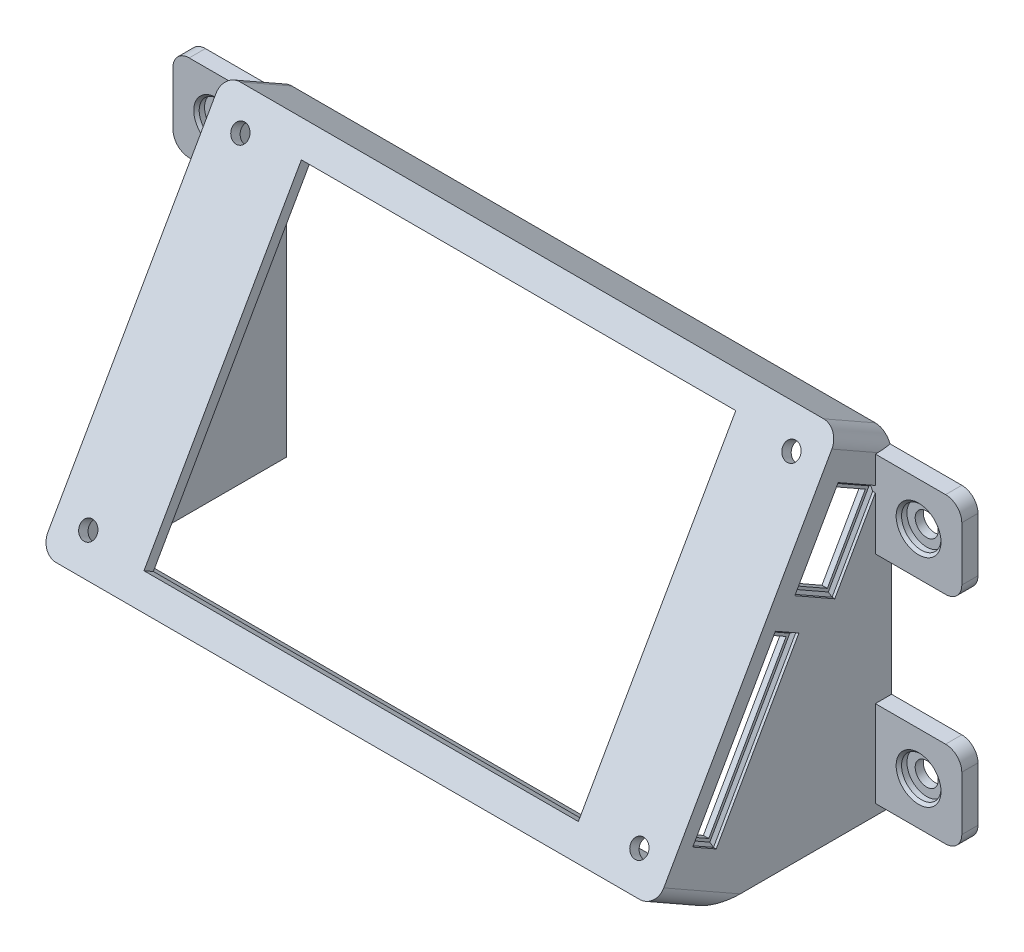
SolidWorks part; units mm, degrees
ref_plane "Front Plane" through (0, 0, 0) normal (0, 0, 1) x (1, 0, 0)
ref_plane "Top Plane" through (0, 0, 0) normal (0, 1, 0) x (1, 0, 0)
ref_plane "Right Plane" through (0, 0, 0) normal (1, 0, 0) x (0, 0, -1)
sketch "Sketch1" plane through (0, 0, 0) normal (1, 0, 0) x (0, 0, -1)
  line L0 (0, 0) -> (0, 60)
  line L1 (0, 60) -> (-34.0735, 0)
  line L2 (-34.0735, 0) -> (0, 0)
  dimension "D1" = 60
  dimension "D2" = 69
extrude "Boss-Extrude1" add sketch "Sketch1" along normal blind 114
sketch "Sketch2" plane through (0, 14.6314, 25.7644) normal (0, 0.4938, 0.8696) x (1, 0, 0)
  line L1 (0, 52.1739) -> (114, 52.1739)
  line L2 (0, 52.1739) -> (0, -16.8261)
  line L3 (0, -16.8261) -> (114, -16.8261)
  line L4 (114, 52.1739) -> (114, -16.8261)
extrude "Boss-Extrude2" add sketch "Sketch2" along normal blind 11
fillet "Fillet1" radius 3 4 edges at (0, 2.716, 38.8561) (0, 62.716, 4.7826) (114, 2.716, 38.8561) (114, 62.716, 4.7826)
shell "Shell1" thickness 2 removed face at (57, 0, 21.11) removed face at (57, 39.0882, 0)
sketch "Sketch3" plane through (0, 20.0634, 35.3296) normal (0, 0.4938, 0.8696) x (1, 0, 0)
  line L0 (0, 49.1739) -> (0, -13.8261) construction
  line L1 (111, 52.1739) -> (3, 52.1739) construction
  line L2 (114, -13.8261) -> (114, 49.1739) construction
  line L3 (3, -16.8261) -> (111, -16.8261) construction
  circle A0 centre (6, 46.1739) radius 1.6
  circle A1 centre (6, -10.8261) radius 1.6
  circle A2 centre (108, -10.8261) radius 1.6
  circle A3 centre (108, 46.1739) radius 1.6
  point P8 (0, 0)
  point P9 (0, 0)
  point P10 (0, 0)
  point P11 (0, 0)
  dimension "D1" = 3.2
  dimension "D2" = 6
  dimension "D3" = 6
  dimension "D4" = 6
  dimension "D5" = 6
extrude "Cut-Extrude1" cut sketch "Sketch3" against normal up to surface (2 mm away) up to face at (57, 34.4444, 24.8628)
sketch "Sketch4" plane through (0, 20.0634, 35.3296) normal (0, 0.4938, 0.8696) x (1, 0, 0)
  line L0 (111, 52.1739) -> (3, 52.1739) construction
  line L1 (16.8, 47.1739) -> (97.2, 47.1739)
  line L2 (16.8, 47.1739) -> (16.8, -11.8261)
  line L3 (16.8, -11.8261) -> (97.2, -11.8261)
  line L4 (97.2, 47.1739) -> (97.2, -11.8261)
  line L5 (0, 49.1739) -> (0, -13.8261) construction
  dimension "D1" = 59
  dimension "D2" = 80.4
  dimension "D3" = 5
  dimension "D4" = 16.8
extrude "Cut-Extrude2" cut sketch "Sketch4" against normal up to surface (2 mm away) up to face at (108, 57.8357, 11.5791)
sketch "Sketch5" plane through (114, 0, 0) normal (1, 0, 0) x (0, 0, -1)
  line L0 (-35.4396, 12.2758) -> (-32.8309, 10.7944)
  line L1 (-32.8309, 10.7944) -> (-18.5102, 36.0118)
  line L2 (-18.5102, 36.0118) -> (-21.1189, 37.4932)
  line L3 (-21.1189, 37.4932) -> (-35.4396, 12.2758)
  line L4 (-42.1572, 8.0407) -> (-11.0467, 62.8233) construction
  line L5 (-34.0735, 0) -> (-43.6387, 5.432) construction
  line L6 (-16.5397, 43.1267) -> (-9.5077, 55.5093)
  line L7 (-9.5077, 55.5093) -> (-3.8555, 52.2995)
  line L8 (-3.8555, 52.2995) -> (-10.8875, 39.9169)
  line L9 (-10.8875, 39.9169) -> (-16.5397, 43.1267)
  line L10 (0, 56.55) -> (-11.0467, 62.8233) construction
  line L11 (-9.5652, 65.432) -> (0, 60) construction
  dimension "D1" = 3
  dimension "D2" = 29
  dimension "D3" = 10
  dimension "D4" = 3.75
  dimension "D5" = 8.6
  dimension "D6" = 4.95
  dimension "D7" = 6.5
  dimension "D8" = 14.24
extrude "Cut-Extrude3" cut sketch "Sketch5" against normal up to surface (2 mm away)
sketch "Sketch6" plane through (114, 0, 0) normal (1, 0, 0) x (0, 0, -1)
  line L8 (-36.803, 11.9001) -> (-32.4552, 9.431)
  line L9 (-32.4552, 9.431) -> (-17.1468, 36.3875)
  line L10 (-17.1468, 36.3875) -> (-21.4946, 38.8566)
  line L11 (-21.4946, 38.8566) -> (-36.803, 11.9001)
  line L12 (-36.803, 11.9001) -> (-32.4552, 9.431)
  line L13 (-32.4552, 9.431) -> (-17.1468, 36.3875)
  line L14 (-17.1468, 36.3875) -> (-21.4946, 38.8566)
  line L15 (-21.4946, 38.8566) -> (-36.803, 11.9001)
  line L20 (-10.5118, 38.5535) -> (-2.4921, 52.6753)
  line L21 (-2.4921, 52.6753) -> (-9.8835, 56.8727)
  line L22 (-9.8835, 56.8727) -> (-17.9031, 42.751)
  line L23 (-17.9031, 42.751) -> (-10.5118, 38.5535)
  line L24 (-10.5118, 38.5535) -> (-2.4921, 52.6753)
  line L25 (-2.4921, 52.6753) -> (-9.8835, 56.8727)
  line L26 (-9.8835, 56.8727) -> (-17.9031, 42.751)
  line L27 (-17.9031, 42.751) -> (-10.5118, 38.5535)
  dimension "D1" = 1
  dimension "D2" = 1
extrude "Cut-Extrude4" cut sketch "Sketch6" against normal blind 1
ref_plane "Plane1" through (57, 0, 0) normal (1, 0, 0) x (0, 0, -1)
chamfer "Chamfer3" distance 0.5 angle 45 8 edges at (113, 37.6221, 19.3207) (113, 22.9093, 24.801) (113, 25.3783, 29.1488) (113, 10.6655, 34.6291) (113, 40.6523, 14.2074) (113, 49.8119, 13.8933) (113, 54.774, 6.1878) (113, 45.6144, 6.502)
sketch "Sketch7" plane through (114, 0, 0) normal (1, 0, 0) x (0, 0, -1)
  line L0 (0, 0) -> (0, 56.55) construction
  line L1 (0, 58) -> (-3, 58)
  line L2 (0, 58) -> (0, 42)
  line L3 (0, 42) -> (-3, 42)
  line L4 (-3, 58) -> (-3, 42)
  line L5 (-27.9983, 0) -> (0, 0) construction
  line L6 (0, 18) -> (-3, 18)
  line L7 (0, 18) -> (0, 2)
  line L8 (0, 2) -> (-3, 2)
  line L9 (-3, 18) -> (-3, 2)
  dimension "D1" = 16
  dimension "D2" = 2
  dimension "D3" = 24
  dimension "D4" = 3
extrude "Boss-Extrude3" add sketch "Sketch7" along normal blind 16 and the other way blind 2
sketch "Sketch8" plane through (0, 0, 3) normal (0, 0, 1) x (1, 0, 0)
  line L0 (122, 58) -> (122, 42) construction
  line L1 (114, 58) -> (130, 58) construction
  line L2 (114, 42) -> (130, 42) construction
  line L3 (122, 18) -> (122, 2) construction
  line L4 (114, 18) -> (130, 18) construction
  line L5 (114, 2) -> (130, 2) construction
  circle A0 centre (122, 50) radius 2.125
  circle A1 centre (122, 10) radius 2.125
  point P16 (122, 12.9049)
  point P17 (0, 0)
  dimension "D1" = 4.25
extrude "Cut-Extrude5" cut sketch "Sketch8" against normal blind 3
sketch "Sketch9" plane through (0, 0, 3) normal (0, 0, 1) x (1, 0, 0)
  circle A0 centre (122, 50) radius 3.65
  circle A1 centre (122, 10) radius 3.65
  dimension "D1" = 7.3
extrude "Cut-Extrude6" cut sketch "Sketch9" against normal blind 1.5
chamfer "Chamfer4" distance 0.5 angle 45 2 edges at (125.65, 10, 3) (125.65, 50, 3)
fillet "Fillet2" radius 3 4 edges at (130, 18, 1.5) (130, 2, 1.5) (130, 58, 1.5) (130, 42, 1.5)
mirror "Mirror1" about plane through (57, 0, 0) normal (1, 0, 0) of "Fillet2", "Chamfer4", "Cut-Extrude6", "Cut-Extrude5", "Boss-Extrude3"
